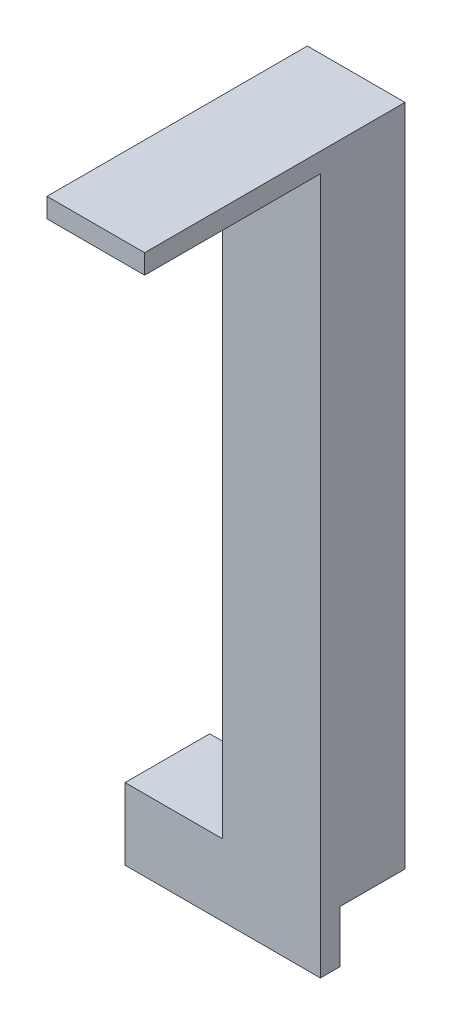
SolidWorks part; units mm, degrees
ref_plane "前视基准面" through (0, 0, 0) normal (0, 0, 1) x (1, 0, 0)
ref_plane "上视基准面" through (0, 0, 0) normal (0, 1, 0) x (1, 0, 0)
ref_plane "右视基准面" through (0, 0, 0) normal (1, 0, 0) x (0, 0, -1)
sketch "草图1" plane through (0, 0, 0) normal (0, 1, 0) x (1, 0, 0)
  line L1 (0, 0) -> (30, 0)
  line L2 (0, 0) -> (0, -13)
  line L3 (0, -13) -> (30, -13)
  line L4 (30, 0) -> (30, -13)
  line L5 (0, -10) -> (30, -10)
  line L6 (0, -10) -> (0, -13)
  line L7 (0, -13) -> (30, -13)
  line L8 (30, -10) -> (30, -13)
  dimension "D1" = 30
  dimension "D2" = 13
  dimension "D3" = 3
extrude "凸台-拉伸2" add sketch "草图1" against normal blind 11 contours L5 L2 L3 L4 region at (15, 0, 11.5)
extrude "凸台-拉伸3" add sketch "草图1<5>" against normal blind 3 contours L2 L5 L4 L1 region at (15, 0, 5)
sketch "草图1<5>" plane through (0, 0, 0) normal (0, 1, 0) x (1, 0, 0) same geometry as "草图1"
sketch "草图3" plane through (0, 0, 0) normal (-1, 0, 0) x (0, 0, 1)
  line L0 (0, 0) -> (0, 99)
  line L1 (0, 0) -> (13, 0) construction
  line L2 (0, 99) -> (40, 99)
  line L4 (13, 0) -> (0, 0)
  line L5 (13, 0) -> (13, 96)
  line L6 (13, 96) -> (40, 96)
  line L7 (40, 96) -> (40, 99)
  dimension "D1" = 110
  dimension "D2" = 40
  dimension "D3" = 3
extrude "凸台-拉伸4" add sketch "草图3" against normal blind 30 contours L4 L0 L2 L7 L6 L5
extrude "切除-拉伸1" cut sketch "草图3<4>" against normal blind 15
sketch "草图3<4>" plane through (0, 0, 0) normal (-1, 0, 0) x (0, 0, 1) same geometry as "草图3"
